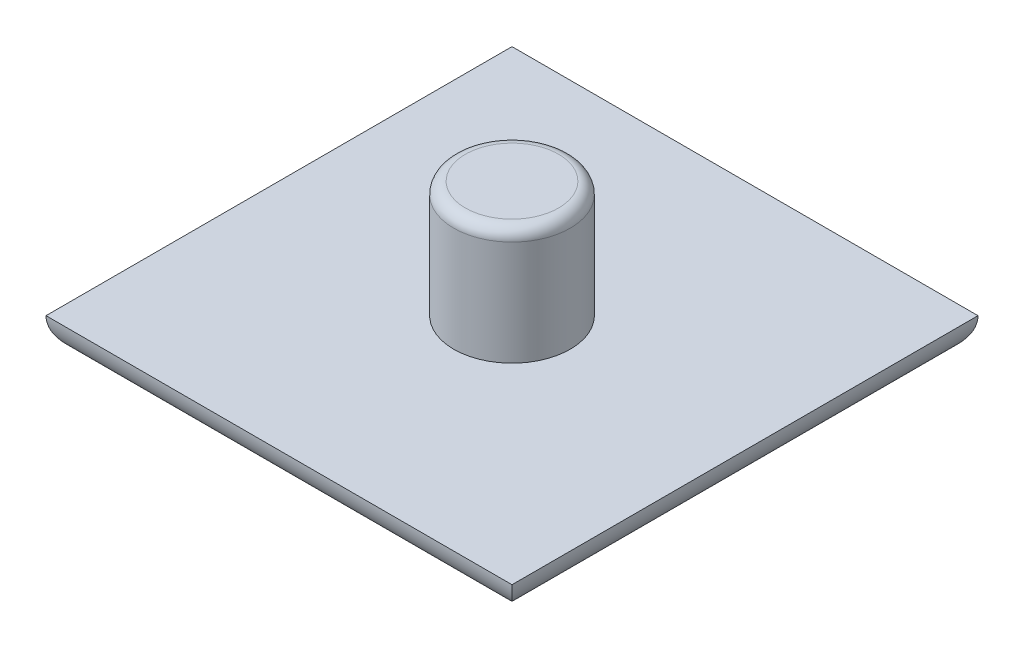
SolidWorks part; units mm, degrees
ref_plane "前视基准面" through (0, 0, 0) normal (0, 0, 1) x (1, 0, 0)
ref_plane "上视基准面" through (0, 0, 0) normal (0, 1, 0) x (1, 0, 0)
ref_plane "右视基准面" through (0, 0, 0) normal (1, 0, 0) x (0, 0, -1)
sketch "草图1" plane through (0, 0, 0) normal (0, 1, 0) x (1, 0, 0)
  line L1 (-10, 10) -> (10, 10)
  line L2 (-10, 10) -> (-10, -10)
  line L3 (-10, -10) -> (10, -10)
  line L4 (10, 10) -> (10, -10)
  line L5 (-10, 10) -> (10, -10) construction
  line L6 (-10, -10) -> (10, 10) construction
  point P0 (0, 0)
  dimension "D1" = 20
  dimension "D2" = 20
extrude "凸台-拉伸1" add sketch "草图1" along normal blind 1.5
sketch "草图2" plane through (0, 1.5, 0) normal (0, 1, 0) x (1, 0, 0)
  circle A0 centre (0, 0) radius 2.5
  dimension "D1" = 5
extrude "凸台-拉伸2" add sketch "草图2" along normal blind 5
fillet "圆角1" radius 1.5 4 edges at (0, 0, 10) (10, 0, 0) (0, 0, -10) (-10, 0, 0)
fillet "圆角2" radius 0.5 1 edges at (0, 6.5, 2.5)
